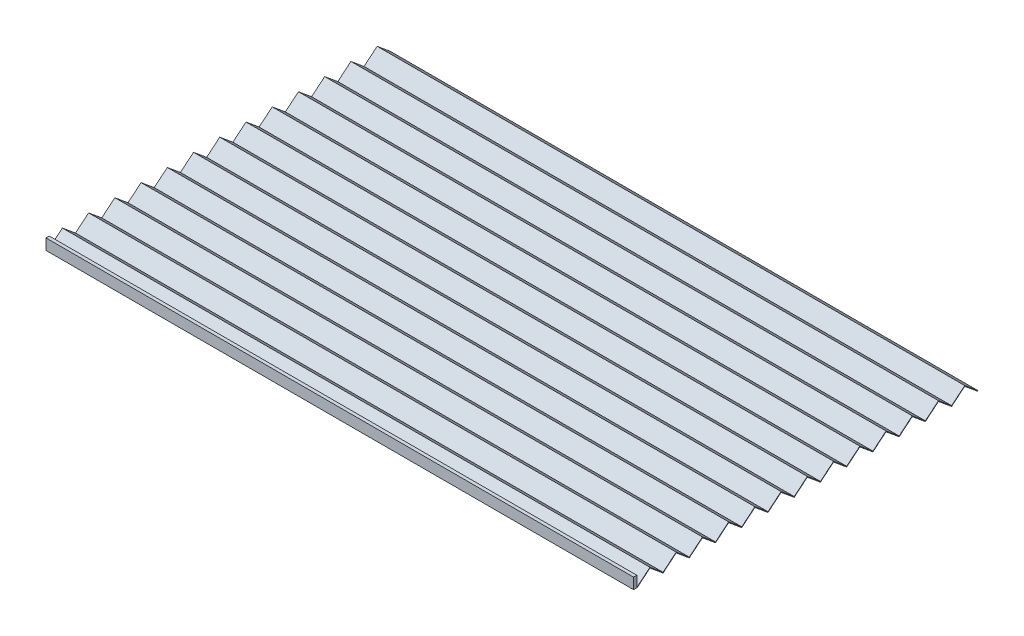
SolidWorks part; units mm, degrees
ref_plane "Front Plane" through (0, 0, 0) normal (0, 0, 1) x (1, 0, 0)
ref_plane "Top Plane" through (0, 0, 0) normal (0, 1, 0) x (1, 0, 0)
ref_plane "Right Plane" through (0, 0, 0) normal (1, 0, 0) x (0, 0, -1)
sketch "Sketch2" plane through (0, 0, 0) normal (0, 0, 1) x (1, 0, 0)
  line L1 (-270, 10) -> (270, 10)
  line L2 (-270, 10) -> (-270, 0)
  line L3 (-270, 0) -> (270, 0)
  line L4 (270, 10) -> (270, 0)
  point P4 (0, 0)
  dimension "D1" = 10
  dimension "D2" = 540
extrude "Boss-Extrude1" add sketch "Sketch2" along normal blind 3
sketch "Sketch3" plane through (270, 0, 0) normal (1, 0, 0) x (0, 0, -1)
  line L0 (0, 10) -> (313.3645, 10) construction
  line L1 (0, 0) -> (313.3645, 0) construction
  line L2 (313.3645, 10) -> (313.3645, 0) construction
  line L3 (0, 0) -> (12.0525, 10)
  line L4 (12.0525, 10) -> (24.105, 0)
  line L5 (24.105, 0) -> (36.1574, 10)
  line L6 (36.1574, 10) -> (48.2099, 0)
  line L7 (48.2099, 0) -> (60.2624, 10)
  line L8 (60.2624, 10) -> (72.3149, 0)
  line L9 (72.3149, 0) -> (84.3674, 10)
  line L10 (84.3674, 10) -> (96.4199, 0)
  line L11 (96.4199, 0) -> (108.4723, 10)
  line L12 (108.4723, 10) -> (120.5248, 0)
  line L13 (120.5248, 0) -> (132.5773, 10)
  line L14 (132.5773, 10) -> (144.6298, 0)
  line L15 (144.6298, 0) -> (156.6823, 10)
  line L16 (156.6823, 10) -> (168.7347, 0)
  line L17 (168.7347, 0) -> (180.7872, 10)
  line L18 (180.7872, 10) -> (192.8397, 0)
  line L20 (192.8397, 0) -> (204.8922, 10)
  line L21 (204.8922, 10) -> (216.9447, 0)
  line L22 (216.9447, 0) -> (228.9971, 10)
  line L23 (228.9971, 10) -> (241.0496, 0)
  line L24 (241.0496, 0) -> (253.1021, 10)
  line L25 (253.1021, 10) -> (265.1546, 0)
  line L26 (265.1546, 0) -> (277.2071, 10)
  line L27 (277.2071, 10) -> (289.2596, 0)
  line L28 (289.2596, 0) -> (301.312, 10)
  line L29 (301.312, 10) -> (313.3645, 0)
  line L30 (313.3645, 10) -> (313.3645, 0) construction
extrude "Extrude-Thin1" add sketch "Sketch3" against normal through all thin thin type mid plane wall 0.5
